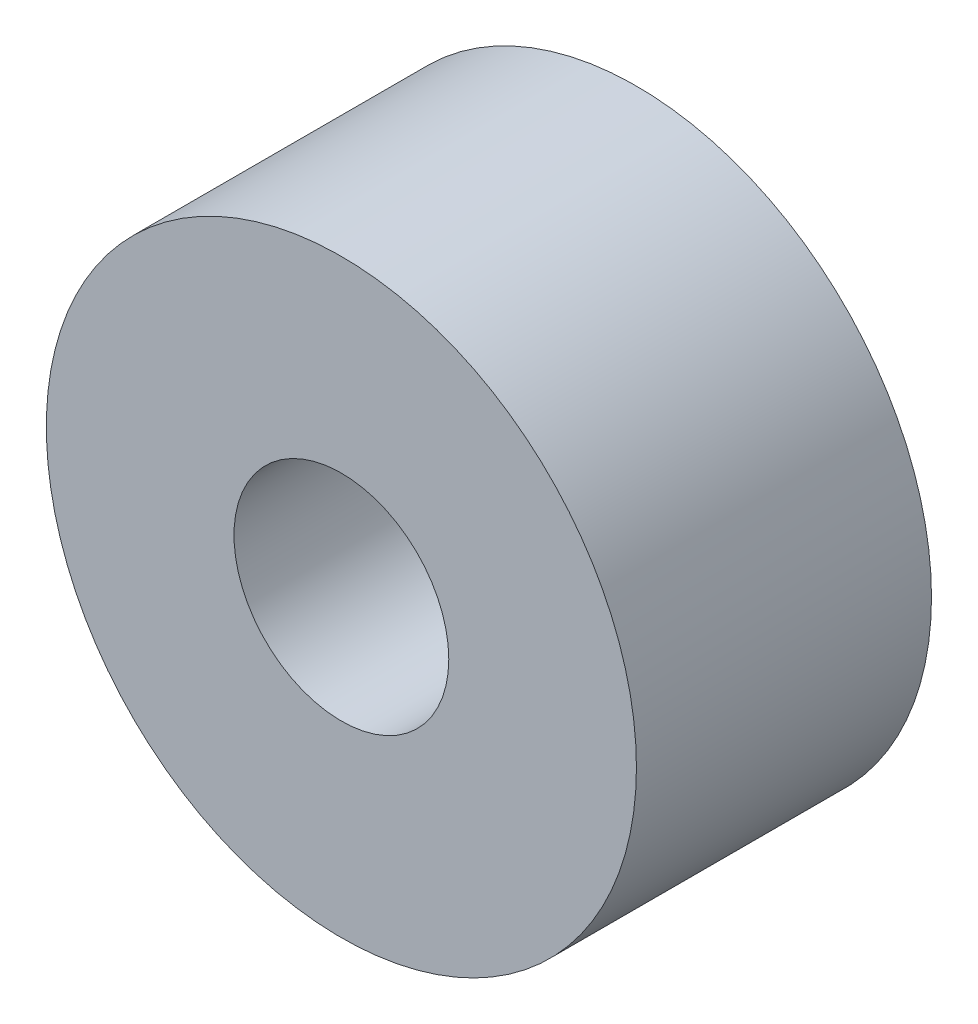
SolidWorks part; units mm, degrees
material "Nylon 6/10"
ref_plane "Front Plane" through (0, 0, 0) normal (0, 0, 1) x (1, 0, 0)
ref_plane "Top Plane" through (0, 0, 0) normal (0, 1, 0) x (1, 0, 0)
ref_plane "Right Plane" through (0, 0, 0) normal (1, 0, 0) x (0, 0, -1)
sketch "Sketch1" plane through (0, 0, 0) normal (0, 0, 1) x (1, 0, 0)
  circle A0 centre (0, 0) radius 3.175
  circle A1 centre (0, 0) radius 1.1557
  dimension "OD" = 6.35
  dimension "ID" = 2.3114
extrude "Extrude1" add sketch "Sketch1" along normal mid plane 3.175
sketch "Sketch2" plane through (0, 0, 0) normal (1, 0, 0) x (0, 0, -1)
  line L0 (-1.5875, -1.1557) -> (1.5875, -1.1557) construction
  line L3 (1.5875, 1.1557) -> (-1.5875, 1.1557) construction
  line L5 (-1.5875, -1.1557) -> (1.5875, -1.1557)
  line L6 (1.5875, 1.1557) -> (-1.5875, 1.1557)
sketch "Sketch4" plane through (0, 0, 1.5875) normal (0, 0, 1) x (1, 0, 0)
  line L0 (0, 0) -> (-0.8172, 0.8172)
  line L1 (0, -0.8731) -> (0, 0.8731) construction
  circle A0 centre (0, 0) radius 1.1557 construction
  dimension "D1" = 45
